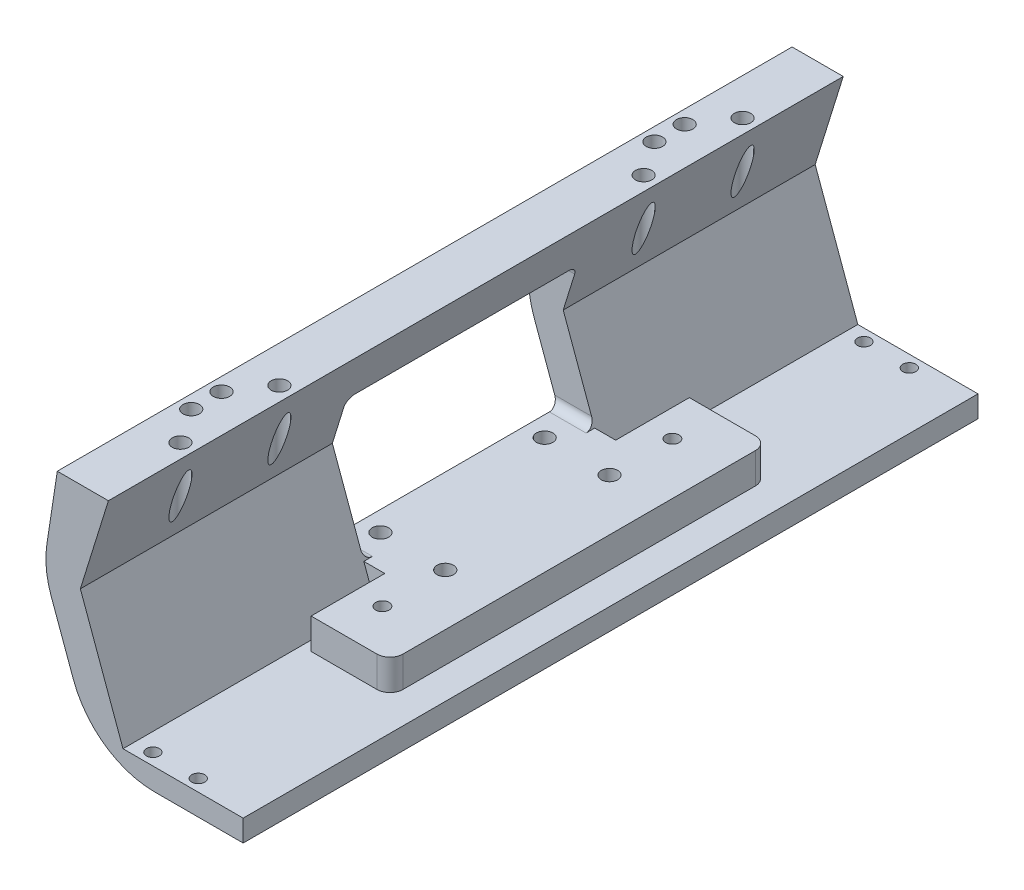
SolidWorks part; units mm, degrees
ref_plane "前视基准面" through (0, 0, 0) normal (0, 0, 1) x (1, 0, 0)
ref_plane "上视基准面" through (0, 0, 0) normal (0, 1, 0) x (1, 0, 0)
ref_plane "右视基准面" through (0, 0, 0) normal (1, 0, 0) x (0, 0, -1)
other "Configuration Table"
sketch "草图1" plane through (0, 0, 0) normal (0, 1, 0) x (1, 0, 0)
  line L0 (77.9817, 90) -> (77.9817, -80)
  line L1 (77.9817, 90) -> (105.7807, 90)
  line L3 (77.9817, -80) -> (105.7807, -80)
  line L4 (105.7807, 90) -> (105.7807, -80)
  circle A0 centre (82.1409, 87.25) radius 1.5
  circle A1 centre (92.6409, 87.25) radius 1.5
  circle A2 centre (82.1409, -77.25) radius 1.5
  circle A3 centre (92.6409, -77.25) radius 1.5
  point P0 (0, 0)
extrude "凸台-拉伸1" add sketch "草图1" along normal blind 5
sketch "草图2" plane through (0, 0, 80) normal (0, 0, 1) x (1, 0, 0)
  line L0 (70.1541, 3.1157) -> (59.6018, 32.1079)
  line L1 (77.9817, 5) -> (68.1152, 32.1079)
  line L2 (77.9817, 5) -> (105.7807, 5) construction
  line L3 (77.9817, 5) -> (63.6209, 44.4558) construction
  line L4 (70.4641, 2.2638) -> (56.1034, 41.7197) construction
  line L5 (70.1541, 3.1157) -> (71.2881, 0)
  line L6 (71.2881, 0) -> (77.9817, 0)
  line L7 (62.7747, 53) -> (74.6027, 53)
  line L9 (77.9817, 5) -> (77.9817, 0)
  line L13 (59.6018, 32.1079) -> (60.4325, 37.5776)
  line L14 (68.1152, 32.1079) -> (74.6027, 53)
  line L17 (62.7721, 53) -> (251.9817, 53) construction
  line L18 (60.4325, 37.5776) -> (62.7747, 53)
  dimension "D1" = 8
  dimension "D2" = 110
extrude "凸台-拉伸2" add sketch "草图2" against normal up to surface (170 mm away) up to face at (91.8812, 2.5, -90)
ref_plane "中间面" through (0, 0, -5) normal (0, 0, -1) x (-1, 0, 0)
fillet "圆角1" radius 20 1 edges at (59.6018, 32.1079, -5)
fillet "圆角2" radius 20 1 edges at (71.2881, 0, -5)
sketch "草图3" plane through (0, 53, 0) normal (0, 1, 0) x (1, 0, 0)
  circle A0 centre (71.2881, 70.0248) radius 1.9
  circle A1 centre (65.8418, 62.079) radius 1.9
  circle A2 centre (65.8418, 55.079) radius 1.9
  circle A3 centre (71.2881, 47.1331) radius 1.9
  circle A4 centre (71.2881, -37.1331) radius 1.9
  circle A5 centre (65.8418, -45.079) radius 1.9
  circle A6 centre (65.8418, -52.079) radius 1.9
  circle A7 centre (71.2881, -60.0248) radius 1.9
  dimension "D1" = 3.8
extrude "切除-拉伸1" cut sketch "草图3" against normal blind 22
sketch "草图5" plane through (0, 0, 0) normal (1, 0, 0) x (0, 0, -1)
  line L0 (5, 53) -> (5, -16.1066) construction
  line L1 (90, 53) -> (-80, 53) construction
  line L2 (5, -25.1016) -> (5, 25.1016) construction
  line L4 (-21.7056, 42.6301) -> (31.7056, 42.6301)
  line L5 (-21.7056, 42.6301) -> (-21.7056, 12.0981)
  line L6 (-21.7056, 12.0981) -> (31.7056, 12.0981)
  line L7 (31.7056, 42.6301) -> (31.7056, 12.0981)
extrude "切除-拉伸2" cut sketch "草图5" along normal blind 138
sketch "草图6" plane through (0, 5, 0) normal (0, 1, 0) x (1, 0, 0)
  line L0 (75.3982, 31.7056) -> (80.2506, 31.7056)
  line L1 (80.2506, -21.7056) -> (80.2506, -38.7564)
  line L4 (75.3982, -21.7056) -> (75.3982, 31.7056)
  line L5 (75.3982, 31.7056) -> (75.3982, -21.7056) construction
  line L8 (98.4953, 5) -> (17.5167, 5) construction
  line L11 (80.2506, 31.7056) -> (80.2506, 48.7564)
  line L13 (80.2506, -21.7056) -> (75.3982, -21.7056)
  line L18 (80.2506, 48.7564) -> (98.4953, 48.7564)
  line L19 (98.4953, 48.7564) -> (98.4953, -38.7564)
  line L20 (98.4953, -38.7564) -> (80.2506, -38.7564)
extrude "凸台-拉伸3" add sketch "草图6" along normal up to surface (7.0981 mm away) up to face at (71.1588, 12.0981, -5)
fillet "圆角3" radius 2 4 edges at (71.1588, 12.0981, -31.7056) (71.1588, 12.0981, 21.7056) (66.2912, 42.6301, 21.7056) (66.2912, 42.6301, -31.7056)
sketch "草图7" plane through (0, 12.0981, 0) normal (0, 1, 0) x (1, 0, 0)
  line L0 (71.5304, -14) -> (86.5304, -14) construction
  line L1 (86.5304, -14) -> (86.5304, 24) construction
  line L2 (86.5304, 24) -> (71.5304, 24) construction
  line L3 (71.5304, 24) -> (71.5304, -14) construction
  line L4 (92.3883, 5) -> (50092.3883, 5) construction
  circle A0 centre (71.5304, -14) radius 1.9
  circle A1 centre (71.5304, 24) radius 1.9
  circle A2 centre (86.5304, 24) radius 1.9
  circle A3 centre (86.5304, -14) radius 1.9
  circle A4 centre (86.5304, 38.5456) radius 1.55
  circle A5 centre (86.5304, -28.5456) radius 1.55
  point P17 (0, 0)
  dimension "D3" = 3.8
  dimension "D4" = 3.1
  dimension "D1" = 38
  dimension "D2" = 15
extrude "切除-拉伸3" cut sketch "草图7" against normal blind 20
fillet "圆角4" radius 3 2 edges at (98.4953, 8.5491, -48.7564) (98.4953, 8.5491, 38.7564)
